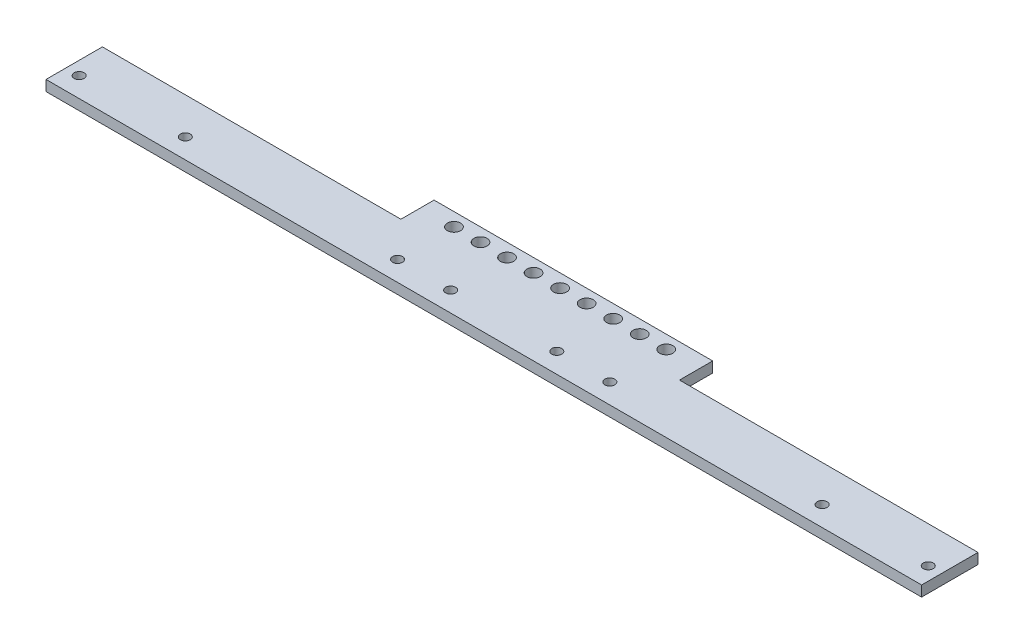
SolidWorks part; units mm, degrees
ref_plane "Front" through (0, 0, 0) normal (0, 0, 1) x (1, 0, 0)
ref_plane "Top" through (0, 0, 0) normal (0, 1, 0) x (1, 0, 0)
ref_plane "Right" through (0, 0, 0) normal (1, 0, 0) x (0, 0, -1)
sketch "Sketch1" plane through (0, 0, 0) normal (0, 1, 0) x (1, 0, 0)
  line L0 (0, 25.5356) -> (0, -1.4644)
  line L3 (0, 25.5356) -> (264, 25.5356)
  line L7 (0, -1.4644) -> (264, -1.4644)
  line L8 (264, -1.4644) -> (264, 25.5356)
  line L9 (264, -1.4644) -> (264, 10.5356)
  line L10 (264, 21.5356) -> (260, 21.5356)
  line L11 (0, 21.5356) -> (4, 21.5356)
  line L12 (4, 21.5356) -> (260, 21.5356)
  line L13 (4, 21.5356) -> (132, 21.5356)
  line L14 (132, 21.5356) -> (260, 21.5356)
  line L15 (264, 10.5356) -> (264, -1.4644)
  line L16 (264, 4.5356) -> (260, 4.5356)
  line L17 (132, 25.5356) -> (132, 23.5356)
  line L18 (4, 21.5356) -> (68, 21.5356)
  line L19 (68, 21.5356) -> (36, 21.5356)
  line L20 (36, 21.5356) -> (36, 4.5356)
  line L21 (196, 21.5356) -> (260, 21.5356)
  line L22 (228, 21.5356) -> (228, 4.5356)
  line L23 (132, 21.5356) -> (132, 4.5356)
  line L24 (132, 21.5356) -> (164, 21.5356)
  circle A0 centre (4, 21.5356) radius 2
  circle A1 centre (260, 21.5356) radius 2
  circle A2 centre (132, 21.5356) radius 2
  circle A3 centre (68, 21.5356) radius 2
  circle A4 centre (196, 21.5356) radius 2
  circle A5 centre (260, 4.5356) radius 1.5
  circle A6 centre (4, 4.5356) radius 1.5
  circle A7 centre (36, 4.5356) radius 1.5
  circle A8 centre (228, 4.5356) radius 1.5
  circle A9 centre (132, 4.5356) radius 1.5
  circle A10 centre (164, 21.5356) radius 2
  circle A11 centre (100, 21.5356) radius 2
  dimension "D5" = 23
  dimension "D6" = 128
  dimension "D9" = 4
  dimension "D10" = 32
  dimension "D1" = 4
  dimension "D2" = 264
  dimension "D3" = 4
  dimension "D4" = 4
  dimension "D7" = 128
  dimension "D8" = 12
extrude "Boss-Extrude1" add sketch "Sketch1" along normal blind 3.175 contours A1 L10 L3 A0 | A1 A0 L10 | A3 L13 A2 L17 L3 L0 L11 A0 | A9 | A0 | A1 region at (65.9183, 0, -23.5857) region at (1, 0, -18.8856) region at (198.0817, 0, -23.5857)
sketch "Sketch2" plane through (0, 3.175, 0) normal (0, 1, 0) x (1, 0, 0)
  line L0 (37.5, 4.5356) -> (228, 4.5356)
  line L1 (132, 21.5356) -> (132, 4.5356)
  line L2 (132, 4.5356) -> (148, 4.5356)
  line L3 (148, 4.5356) -> (116, 4.5356)
  line L4 (116, 4.5356) -> (100, 4.5356)
  line L5 (148, 4.5356) -> (164, 4.5356)
  circle A0 centre (36, 4.5356) radius 1.5 construction
  circle A1 centre (116, 4.5356) radius 1.5
  circle A2 centre (148, 4.5356) radius 1.5
  circle A3 centre (100, 4.5356) radius 1.5
  circle A4 centre (164, 4.5356) radius 1.5
  dimension "D3" = 16
  dimension "D1" = 16
  dimension "D2" = 16
  dimension "D4" = 16
extrude "Cut-Extrude1" cut sketch "Sketch2" against normal blind 10 contours A3 | A1 | A2 | A4
sketch "Sketch3" plane through (0, 3.175, 0) normal (0, 1, 0) x (1, 0, 0)
  line L0 (0, 25.5356) -> (0, 15.5356)
  line L1 (0, 25.5356) -> (90, 25.5356)
  line L2 (0, 15.5356) -> (90, 15.5356)
  line L3 (90, 25.5356) -> (90, 15.5356)
  line L4 (0, 25.5356) -> (0, -1.4644) construction
  line L5 (264, 25.5356) -> (264, 15.5356)
  line L6 (264, 25.5356) -> (174, 25.5356)
  line L7 (264, 15.5356) -> (174, 15.5356)
  line L8 (174, 25.5356) -> (174, 15.5356)
  line L9 (264, -1.4644) -> (264, 25.5356) construction
  line M15 (264, -1.4644) -> (264, 25.5356)
  line M16 (264, 25.5356) -> (0, 25.5356)
  line M17 (0, 25.5356) -> (0, -1.4644)
  dimension "D1" = 90
  dimension "D2" = 90
  dimension "D3" = 10
  dimension "D4" = 10
extrude "Cut-Extrude2" cut sketch "Sketch3" against normal blind 10 contours L3 L2 M16 M17 | L8 L7 M16 M15 region at (45, 3.175, -20.5356) region at (219, 3.175, -20.5356)
sketch "Sketch4" plane through (0, 3.175, 0) normal (0, 1, 0) x (1, 0, 0)
  circle A0 centre (100, 21.5356) radius 2
  circle A1 centre (108, 21.5356) radius 2
  circle A2 centre (116, 21.5356) radius 2
  circle A3 centre (124, 21.5356) radius 2
  circle A4 centre (132, 21.5356) radius 2
  circle A5 centre (140, 21.5356) radius 2
  circle A6 centre (148, 21.5356) radius 2
  circle A7 centre (156, 21.5356) radius 2
  circle A8 centre (164, 21.5356) radius 2
  dimension "D1" = 9
extrude "Cut-Extrude3" cut sketch "Sketch4" against normal blind 10
